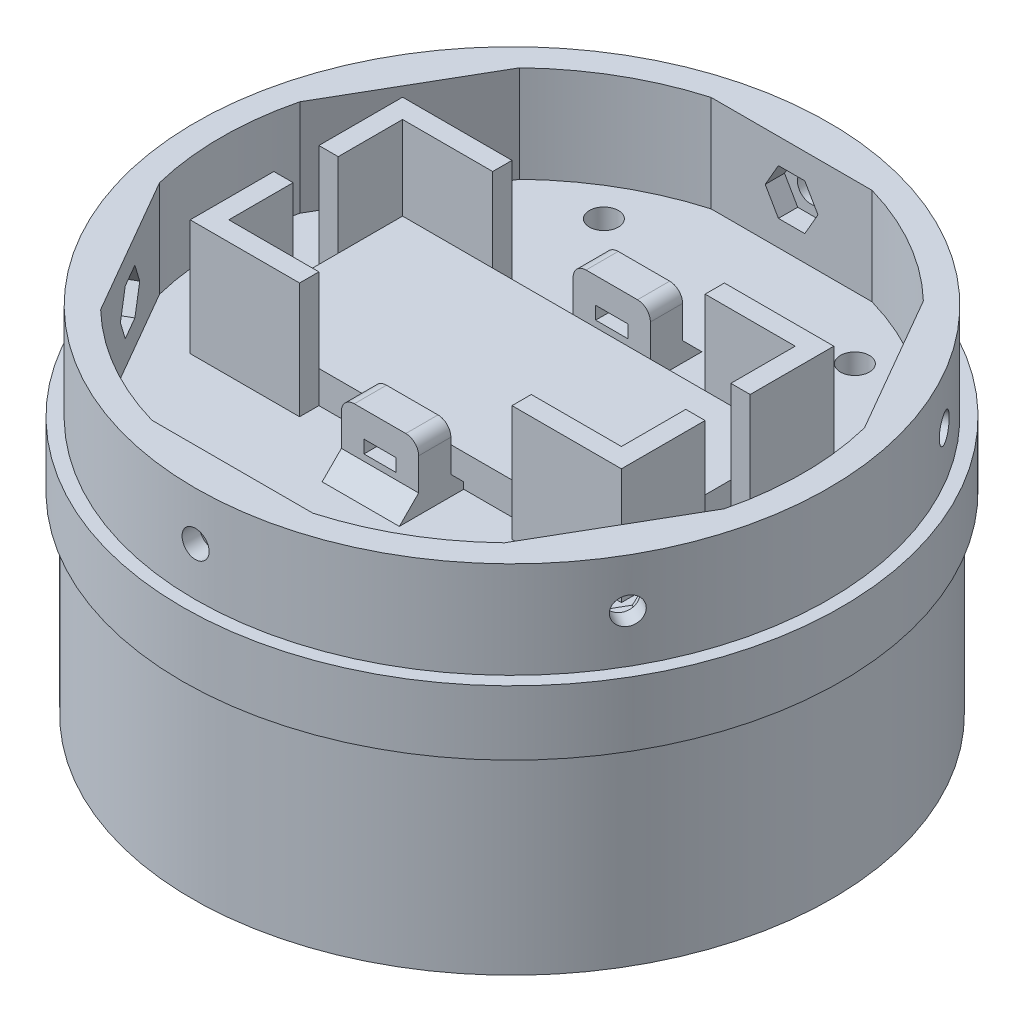
SolidWorks part; units mm, degrees
ref_plane "Спереди" through (0, 0, 0) normal (0, 0, 1) x (1, 0, 0)
ref_plane "Сверху" through (0, 0, 0) normal (0, 1, 0) x (1, 0, 0)
ref_plane "Справа" through (0, 0, 0) normal (1, 0, 0) x (0, 0, -1)
sketch "Эскиз1" plane through (0, 0, 0) normal (0, 0, 1) x (1, 0, 0)
  line L0 (0, 0) -> (0, 84.1878) construction
  line L1 (44.7, 0) -> (49.7, 0)
  line L2 (49.7, 0) -> (49.7, 30)
  line L3 (51.2, 30) -> (49.7, 30)
  line L4 (51.2, 30) -> (51.2, 40)
  line L5 (51.2, 40) -> (0, 40)
  line L6 (44.7, 5) -> (44.7, 10)
  line L7 (44.7, 35) -> (0, 35)
  line L8 (0, 35) -> (0, 40)
  line L12 (44.7, 10) -> (32.7, 10)
  line L13 (32.7, 10) -> (32.7, 15)
  line L14 (32.7, 15) -> (44.7, 15)
  line L15 (44.7, 5) -> (44.7, 0)
  line L16 (44.7, 15) -> (44.7, 35)
  dimension "D1" = 30
  dimension "D2" = 99.4
  dimension "D3" = 10
  dimension "D4" = 5
  dimension "D5" = 5
  dimension "D6" = 102.4
  dimension "D7" = 20
  dimension "D9" = 5
  dimension "D10" = 12
revolve "Повернуть1" add sketch "Эскиз1" angle 360 about L0
sketch "Эскиз2" plane through (0, 0, 0) normal (0, -1, 0) x (1, 0, 0)
  line L0 (0, 0) -> (50000, 0) construction
  line L1 (0, 0) -> (0, 50000) construction
  circle A0 centre (0, 0) radius 43.5 construction
  circle A4 centre (43.5, 0) radius 2.25
  dimension "D1" = 87
  dimension "D2" = 4.5
sketch "Эскиз4" plane through (0, 40, 0) normal (0, 1, 0) x (1, 0, 0)
  line L0 (0, 0) -> (50000, 0) construction
  line L1 (0, 0) -> (0, 50000) construction
  line L3 (-30.5, -13.5) -> (30.5, -13.5)
  line L4 (-30.5, -13.5) -> (-30.5, 13.5)
  line L5 (-30.5, 13.5) -> (30.5, 13.5)
  line L6 (30.5, -13.5) -> (30.5, 13.5)
  line L7 (-30.5, -13.5) -> (30.5, 13.5) construction
  line L8 (-30.5, 13.5) -> (30.5, -13.5) construction
  point P5 (0, 0)
  dimension "D1" = 27
  dimension "D2" = 61
sketch "Эскиз5" plane through (0, 40, 0) normal (0, 1, 0) x (1, 0, 0)
  line L0 (-31.3677, 32.5439) -> (0, 0) construction
  line L2 (0, 0) -> (-41.27, 23.8272) construction
  line L3 (-43.8677, 10.8933) -> (-31.3677, 32.5439)
  line L4 (-12.5, 43.4372) -> (12.5, 43.4372)
  line L5 (31.3677, 32.5439) -> (43.8677, 10.8933)
  line L6 (43.8677, -10.8933) -> (31.3677, -32.5439)
  line L7 (12.5, -43.4372) -> (-12.5, -43.4372)
  line L8 (-31.3677, -32.5439) -> (-43.8677, -10.8933)
  line L9 (0, 0) -> (0, -56.422) construction
  arc A0 (-43.8677, 10.8933) -> (-43.8677, -10.8933) centre (0, 0) ccw
  arc A3 (-12.5, 43.4372) -> (-31.3677, 32.5439) centre (0, 0) ccw
  arc A4 (31.3677, 32.5439) -> (12.5, 43.4372) centre (0, 0) ccw
  arc A5 (43.8677, -10.8933) -> (43.8677, 10.8933) centre (0, 0) ccw
  arc A6 (12.5, -43.4372) -> (31.3677, -32.5439) centre (0, 0) ccw
  arc A7 (-31.3677, -32.5439) -> (-12.5, -43.4372) centre (0, 0) ccw
  arc A8 (-43.8677, 10.8933) -> (-43.8677, -10.8933) centre (0, 0) ccw
  arc A9 (-43.8677, 10.8933) -> (-43.8677, -10.8933) centre (0, 0) ccw
  arc A10 (-43.8677, 10.8933) -> (-43.8677, -10.8933) centre (0, 0) ccw
  arc A11 (-43.8677, 10.8933) -> (-43.8677, -10.8933) centre (0, 0) ccw
  arc A12 (-43.8677, 10.8933) -> (-43.8677, -10.8933) centre (0, 0) ccw
  arc A13 (-31.3677, -32.5439) -> (-12.5, -43.4372) centre (0, 0) ccw
  arc A14 (-31.3677, -32.5439) -> (-12.5, -43.4372) centre (0, 0) ccw
  arc A15 (-31.3677, -32.5439) -> (-12.5, -43.4372) centre (0, 0) ccw
  arc A16 (-31.3677, -32.5439) -> (-12.5, -43.4372) centre (0, 0) ccw
  arc A17 (-31.3677, -32.5439) -> (-12.5, -43.4372) centre (0, 0) ccw
  arc A18 (12.5, -43.4372) -> (31.3677, -32.5439) centre (0, 0) ccw
  arc A19 (12.5, -43.4372) -> (31.3677, -32.5439) centre (0, 0) ccw
  arc A20 (12.5, -43.4372) -> (31.3677, -32.5439) centre (0, 0) ccw
  arc A21 (12.5, -43.4372) -> (31.3677, -32.5439) centre (0, 0) ccw
  arc A22 (12.5, -43.4372) -> (31.3677, -32.5439) centre (0, 0) ccw
  arc A23 (43.8677, -10.8933) -> (43.8677, 10.8933) centre (0, 0) ccw
  arc A24 (43.8677, -10.8933) -> (43.8677, 10.8933) centre (0, 0) ccw
  arc A25 (43.8677, -10.8933) -> (43.8677, 10.8933) centre (0, 0) ccw
  arc A26 (43.8677, -10.8933) -> (43.8677, 10.8933) centre (0, 0) ccw
  arc A27 (43.8677, -10.8933) -> (43.8677, 10.8933) centre (0, 0) ccw
  arc A28 (31.3677, 32.5439) -> (12.5, 43.4372) centre (0, 0) ccw
  arc A29 (31.3677, 32.5439) -> (12.5, 43.4372) centre (0, 0) ccw
  arc A30 (31.3677, 32.5439) -> (12.5, 43.4372) centre (0, 0) ccw
  arc A31 (31.3677, 32.5439) -> (12.5, 43.4372) centre (0, 0) ccw
  arc A32 (31.3677, 32.5439) -> (12.5, 43.4372) centre (0, 0) ccw
  arc A33 (-12.5, 43.4372) -> (-31.3677, 32.5439) centre (0, 0) ccw
  arc A34 (-12.5, 43.4372) -> (-31.3677, 32.5439) centre (0, 0) ccw
  arc A35 (-12.5, 43.4372) -> (-31.3677, 32.5439) centre (0, 0) ccw
  arc A36 (-12.5, 43.4372) -> (-31.3677, 32.5439) centre (0, 0) ccw
  arc A37 (-12.5, 43.4372) -> (-31.3677, 32.5439) centre (0, 0) ccw
  circle A38 centre (0, 0) radius 49.2
  circle A39 centre (0, 0) radius 51.2 construction
  point P24 (0, 0)
  dimension "D1" = 4
  dimension "D6" = 6
  dimension "D3" = 25
  dimension "D4" = 12.5
  dimension "D5" = 6
extrude "Бобышка-Вытянуть3" add sketch "Эскиз5" along normal blind 15 contours A38 A7 L8 A0 L3 A3 L4 A4 L5 A5 L6 A6 L7
sketch "Эскиз6" plane through (-37.6177, 0, -21.7186) normal (0.866, 0, 0.5) x (0.5, 0, -0.866)
  line L1 (4.0992, 47.5) -> (2.0496, 51.05)
  line L2 (2.0496, 51.05) -> (-2.0496, 51.05)
  line L3 (-2.0496, 51.05) -> (-4.0992, 47.5)
  line L4 (-12.5, 40) -> (12.5, 40)
  line L5 (12.5, 40) -> (12.5, 55)
  line L6 (12.5, 55) -> (-12.5, 55)
  line L7 (-12.5, 55) -> (-12.5, 40)
  line L8 (-12.5, 40) -> (12.5, 40)
  line L10 (12.5, 55) -> (-12.5, 55)
  line L12 (-4.0992, 47.5) -> (-2.0496, 43.95)
  line L13 (-2.0496, 43.95) -> (2.0496, 43.95)
  line L14 (2.0496, 43.95) -> (4.0992, 47.5)
  circle A0 centre (0, 47.5) radius 3.55 construction
  dimension "D2" = 7.1
  dimension "D3" = 7.5
  dimension "D1" = 0
sketch "Эскиз8" plane through (-37.6177, 0, -21.7186) normal (0.866, 0, 0.5) x (0.5, 0, -0.866)
  line L0 (0, 0) -> (0, 55) construction
  line L1 (12.5, 55) -> (-12.5, 55) construction
  circle A0 centre (0, 47.5) radius 2.1
  dimension "D1" = 4.2
sketch "Эскиз9" plane through (0, 0, 0) normal (0, -1, 0) x (1, 0, 0)
  line L0 (-200000, 0) -> (250000, 0) construction
  line L1 (0, 0) -> (39, 0) construction
  line L2 (0, 0) -> (39, 0) construction
  circle A1 centre (0, 0) radius 39 construction
  circle A2 centre (39, 0) radius 2.25
  dimension "D1" = 78
  dimension "D4" = 4.5
extrude "Вырез-Вытянуть3" cut sketch "Эскиз9" against normal blind 56
sketch "Эскиз10" plane through (0, 40, 0) normal (0, 1, 0) x (1, 0, 0)
  line L0 (30.5, -13.5) -> (30.5, 13.5) construction
  line L1 (-30.5, -13.5) -> (30.5, -13.5) construction
  line L2 (-30.5, -13.5) -> (-30.5, 13.5) construction
  line L3 (-30.5, 13.5) -> (30.5, 13.5) construction
  line L4 (30.5, -13.5) -> (30.5, -3.5)
  line L5 (-30.5, -13.5) -> (-16.5, -13.5)
  line L6 (-30.5, -13.5) -> (-30.5, -3.5)
  line L7 (-30.5, 13.5) -> (-16.5, 13.5)
  line L8 (-33.5, 3.5) -> (-30.5, 3.5)
  line L9 (-33.5, -16.5) -> (-16.5, -16.5)
  line L10 (-33.5, -16.5) -> (-33.5, -3.5)
  line L11 (-33.5, 16.5) -> (-16.5, 16.5)
  line L12 (33.5, -16.5) -> (33.5, -3.5)
  line L13 (-33.5, -16.5) -> (33.5, 16.5) construction
  line L14 (-33.5, 16.5) -> (33.5, -16.5) construction
  line L15 (-33.5, -3.5) -> (-30.5, -3.5)
  line L16 (-16.5, 16.5) -> (-16.5, 13.5)
  line L17 (16.5, 16.5) -> (16.5, 13.5)
  line L18 (-33.5, 3.5) -> (-33.5, 16.5)
  line L19 (-30.5, 3.5) -> (-30.5, 13.5)
  line L20 (30.5, -3.5) -> (33.5, -3.5)
  line L21 (-16.5, -13.5) -> (-16.5, -16.5)
  line L22 (16.5, 13.5) -> (30.5, 13.5)
  line L23 (16.5, 16.5) -> (33.5, 16.5)
  line L24 (16.5, -13.5) -> (16.5, -16.5)
  line L25 (30.5, 3.5) -> (30.5, 13.5)
  line L26 (33.5, 3.5) -> (33.5, 16.5)
  line L27 (30.5, 3.5) -> (33.5, 3.5)
  line L28 (16.5, -13.5) -> (30.5, -13.5)
  line L29 (16.5, -16.5) -> (33.5, -16.5)
  point P3 (0, 0)
  dimension "D1" = 61
  dimension "D2" = 27
  dimension "D3" = 3
  dimension "D4" = 3
  dimension "D5" = 13
  dimension "D6" = 13
  dimension "D7" = 17
  dimension "D8" = 17
extrude "Бобышка-Вытянуть4" add sketch "Эскиз10" along normal blind 18
sketch "Эскиз14" plane through (0, 0, 0) normal (0, 0, 1) x (1, 0, 0)
  line L0 (0, 0) -> (0, 55) construction
  line L1 (49.2, 55) -> (-49.2, 55) construction
  circle A0 centre (0, 47.5) radius 2.1
  dimension "D1" = 4.2
  dimension "D2" = 7.5
extrude "Бобышка-Вытянуть5" add sketch "Эскиз4" along normal blind 5
sketch "Эскиз11" plane through (0, 40, 0) normal (0, 1, 0) x (1, 0, 0)
  line L0 (0, 0) -> (50000, 0) construction
  line L1 (0, 0) -> (0, 50000) construction
  line L2 (16.5, 13.5) -> (-16.5, 13.5) construction
  line L3 (-6, 20.5) -> (6, 20.5)
  line L4 (-6, 20.5) -> (-6, 15.5)
  line L5 (-6, 15.5) -> (6, 15.5)
  line L6 (6, 20.5) -> (6, 15.5)
  line L7 (-6, 20.5) -> (6, 15.5) construction
  line L8 (-6, 15.5) -> (6, 20.5) construction
  point P5 (0, 18)
  dimension "D1" = 5
  dimension "D2" = 2
  dimension "D3" = 12
extrude "Бобышка-Вытянуть6" add sketch "Эскиз11" along normal blind 10
sketch "Эскиз12" plane through (0, 0, -20.5) normal (0, 0, -1) x (-1, 0, 0)
  line L0 (-6, 50) -> (6, 50) construction
  line L1 (-6, 50) -> (6, 50)
  line L3 (-2.5, 46) -> (2.5, 46)
  line L4 (-2.5, 46) -> (-2.5, 44)
  line L5 (-2.5, 44) -> (2.5, 44)
  line L6 (2.5, 46) -> (2.5, 44)
  line L7 (-2.5, 46) -> (2.5, 44) construction
  line L8 (-2.5, 44) -> (2.5, 46) construction
  point P0 (0, 45)
  dimension "D1" = 5
  dimension "D2" = 2
  dimension "D3" = 4
  dimension "D4" = 6
fillet "Скругление1" radius 2 2 edges at (-6, 50, -18) (6, 50, -18)
extrude "Вырез-Вытянуть4" cut sketch "Эскиз12" against normal blind 6 contours L3 L6 L5 L4
mirror "Зеркальное отражение3" about plane through (0, 0, 0) normal (0, 0, 1) of "Вырез-Вытянуть4", "Бобышка-Вытянуть6", "Скругление1"
chamfer "Фаска5" distance 3 angle 45 4 edges at (0, 40, -20.5) (0, 40, 20.5) (0, 40, -15.5) (0, 40, 15.5)
extrude "Вырез-Вытянуть6" cut sketch "Эскиз6" against normal blind 3 contours L1 L2 L3 L12 L13 L14
extrude "Вырез-Вытянуть7" cut sketch "Эскиз8" against normal blind 36 contours A0
pattern_circular "Круговой массив5" count 6 over 360 about axis through (0, 0, 0) along (0, 1, 0) of "Вырез-Вытянуть7", "Вырез-Вытянуть6"
pattern_circular "Круговой массив6" count 6 over 360 about axis through (0, 0, 0) along (0, 1, 0) of "Вырез-Вытянуть3"
sketch "Эскиз13" plane through (0, 35, 0) normal (0, -1, 0) x (1, 0, 0)
  circle A0 centre (0, 0) radius 44.7095
extrude "Бобышка-Вытянуть7" add sketch "Эскиз13" against normal blind 0.4
chamfer "Фаска6" distance 3 angle 45 2 edges at (0, 35, -44.7) (0, 10, -44.7)
